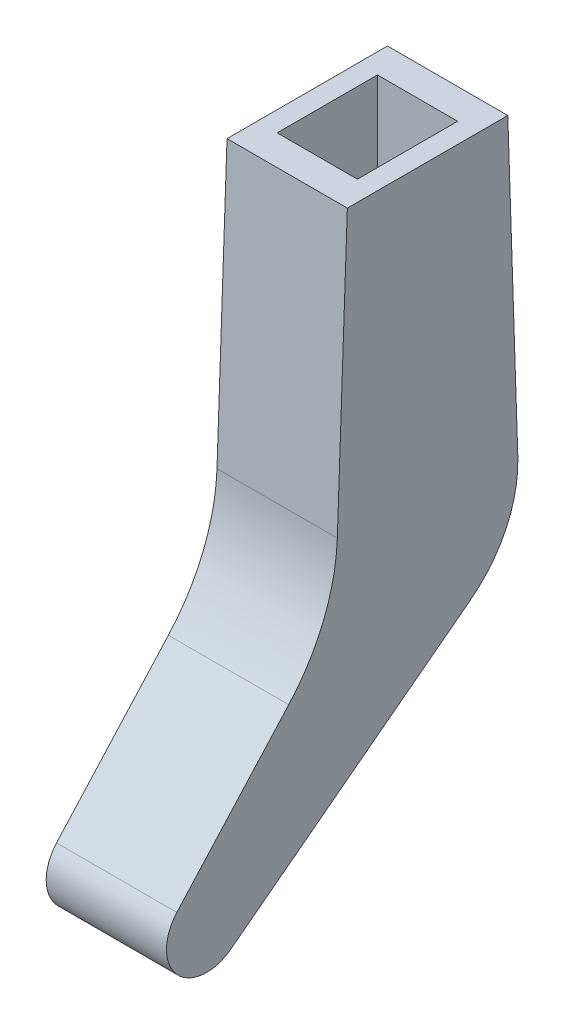
SolidWorks part; units mm, degrees
material "Rubber"
ref_plane "Front Plane" through (0, 0, 0) normal (0, 0, 1) x (1, 0, 0)
ref_plane "Top Plane" through (0, 0, 0) normal (0, 1, 0) x (1, 0, 0)
ref_plane "Right Plane" through (0, 0, 0) normal (1, 0, 0) x (0, 0, -1)
sketch "Sketch1" plane through (0, 0, 0) normal (1, 0, 0) x (0, 0, -1)
  line L0 (-5, 20) -> (-8, 20)
  line L1 (-5, 0) -> (5, 0)
  line L2 (-5, 0) -> (-5, 20)
  line L3 (-5, 20) -> (5, 20)
  line L4 (5, 0) -> (5, 20)
  line L5 (-8, 20) -> (-9, -8)
  line L6 (-13.8475, -19.9623) -> (-25.0029, -32.3197)
  line L7 (-19.6095, -38.1817) -> (4.2532, -20)
  line L8 (9, -10) -> (8, 20)
  line L9 (8, 20) -> (5, 20)
  circle A0 centre (0, 0) radius 5
  arc A1 (-9, -8) -> (-13.8475, -19.9623) centre (-27.8444, -7.327) cw
  arc A2 (-25.0029, -32.3197) -> (-19.6095, -38.1817) centre (-22.0337, -35) ccw
  arc A3 (4.2532, -20) -> (9, -10) centre (-3.0599, -10.402) ccw
  point P17 (-8.0581, 20)
  point P19 (9.2789, -2.5811)
  point P20 (9.0529, -6.4796)
  point P21 (-52.6435, 0.7164)
  point P22 (-40.5528, -2.4049)
  point P23 (-10.0436, -22.9206)
  point P24 (1.3211, -20.9175)
  point P25 (-9.5916, -9.4258)
  dimension "D1" = 10
  dimension "D3" = 4
  dimension "D2" = 20
  dimension "D4" = 30
  dimension "D5" = 3
  dimension "D6" = 3
  dimension "D7" = 30
  dimension "D8" = 35
  dimension "D9" = 9
  dimension "D10" = 28
  dimension "D11" = 9
  dimension "D12" = 40
  dimension "D13" = 11
extrude "Boss-Extrude1" add sketch "Sketch1" along normal mid plane 8 contours L7 A3 L8 L9 L4 A0 L2 L0 L5 A1 L6 A2 region at (0, -13.2175, 5.2441)
extrude "Boss-Extrude2" add sketch "Sketch1<3>" along normal blind 2 from surface contours A0 L4 L3 L2 | L7 A3 L8 L9 L4 A0 L2 L0 L5 A1 L6 A2 | L1 A0 | L1 A0 region at (0, -13.2175, 5.2441) region at (0, 11.9248, 0) region at (0, 2.1221, 0) region at (0, -2.1221, 0) starting at face at (4, -4.7438, 4.5507)
sketch "Sketch1<3>" plane through (0, 0, 0) normal (1, 0, 0) x (0, 0, -1) same geometry as "Sketch1"
extrude "Boss-Extrude3" add sketch "Sketch1<4>" against normal blind 2 from surface contours L1 A0 | L1 A0 | A0 L4 L3 L2 | L7 A3 L8 L9 L4 A0 L2 L0 L5 A1 L6 A2 region at (0, -13.2175, 5.2441) region at (0, 11.9248, 0) region at (0, 2.1221, 0) region at (0, -2.1221, 0) starting at face at (-4, -4.7438, 4.5507)
sketch "Sketch1<4>" plane through (0, 0, 0) normal (1, 0, 0) x (0, 0, -1) same geometry as "Sketch1"
